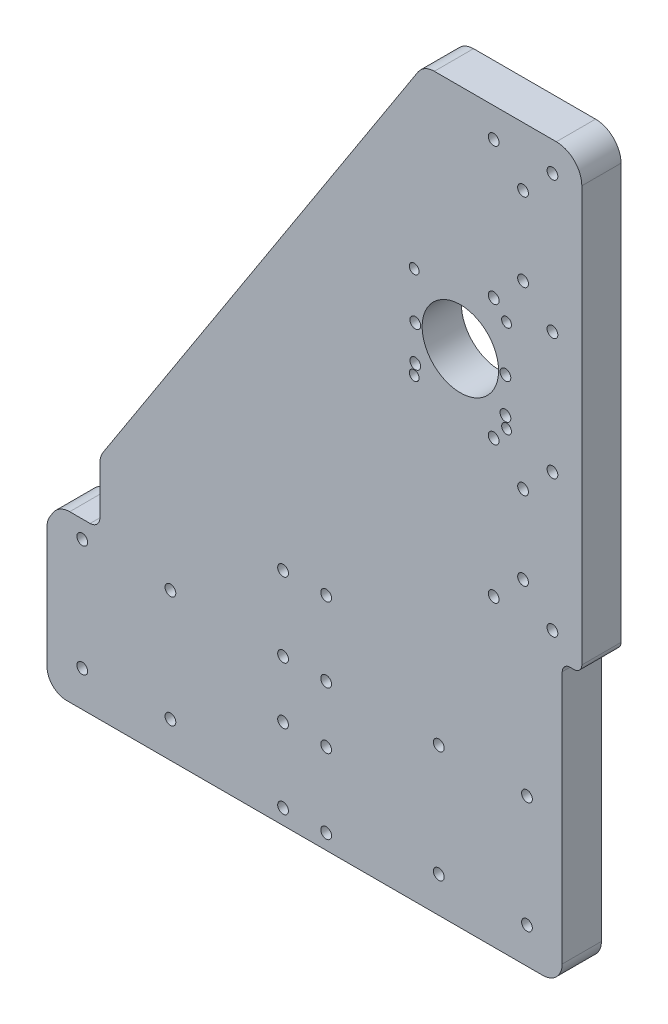
SolidWorks part; units mm, degrees
ref_plane "Front Plane" through (0, 0, 0) normal (0, 0, 1) x (1, 0, 0)
ref_plane "Top Plane" through (0, 0, 0) normal (0, 1, 0) x (1, 0, 0)
ref_plane "Right Plane" through (0, 0, 0) normal (1, 0, 0) x (0, 0, -1)
sketch "Sketch2" plane through (0, 0, 94) normal (0, 0, 1) x (1, 0, 0)
  line L1 (2186.978, 819.9095) -> (2457.8071, 819.9095)
  line L2 (2186.978, 819.9095) -> (2186.978, 457.9095)
  line L3 (2186.978, 457.9095) -> (2457.8071, 457.9095)
  line L4 (2457.8071, 819.9095) -> (2457.8071, 457.9095)
  line L6 (2441.9071, 819.9095) -> (2454.8071, 819.9095) construction
extrude "Boss-Extrude1" add sketch "Sketch2" along normal blind 20
sketch "Sketch3" plane through (0, 0, 114) normal (0, 0, 1) x (1, 0, 0)
  line L0 (2186.978, 819.9095) -> (2186.978, 457.9095) construction
  line L1 (2186.978, 840.163) -> (2194.8071, 840.163)
  line L2 (2186.978, 840.163) -> (2186.978, 445.0092)
  line L3 (2186.978, 445.0092) -> (2194.8071, 445.0092)
  line L4 (2194.8071, 840.163) -> (2194.8071, 445.0092)
extrude "Cut-Extrude1" cut sketch "Sketch3" against normal blind 20
sketch "Sketch4" plane through (0, 0, 114) normal (0, 0, 1) x (1, 0, 0)
  line L0 (2194.8071, 532.657) -> (2380.6092, 819.9095)
  line L1 (2194.8071, 457.9095) -> (2194.8071, 819.9095) construction
  line L2 (2457.8071, 819.9095) -> (2194.8071, 819.9095) construction
  line L3 (2380.6092, 819.9095) -> (2194.8071, 819.9095)
  line L4 (2194.8071, 819.9095) -> (2194.8071, 532.657)
extrude "Cut-Extrude2" cut sketch "Sketch4" against normal blind 20
fillet "Fillet1" radius 10 4 edges at (2457.8071, 457.9095, 104) (2194.8071, 457.9095, 104) (2194.8071, 532.657, 104) (2380.6092, 819.9095, 104)
hole_wizard "M5 Clearance Hole1" positions "Sketch5" profile "Sketch6" hole size "M5" standard "ISO" end condition through all
sketch "Sketch5" plane through (0, 0, 114) normal (0, 0, 1) x (1, 0, 0)
  line L5 (2212.8071, 533.1607) -> (2257.8071, 533.1607) construction
  line L6 (2257.8071, 533.1607) -> (2257.8071, 476.1607) construction
  line L7 (2257.8071, 476.1607) -> (2212.8071, 476.1607) construction
  line L8 (2212.8071, 476.1607) -> (2212.8071, 533.1607) construction
  line L9 (2308.0075, 570.6607) -> (2367.4082, 570.6607) construction
  line L12 (2315.3071, 608.2293) -> (2315.3071, 465.6607) construction
  point P0 (2212.8071, 533.1607)
  point P2 (2257.8071, 533.1607)
  point P4 (2257.8071, 476.1607)
  point P6 (2212.8071, 476.1607)
  point P23 (2439.8071, 476.1607)
  point P24 (2394.8071, 476.1607)
  point P25 (2394.8071, 533.1607)
  point P26 (2439.8071, 533.1607)
  point P27 (2315.3071, 503.6607)
  point P29 (2337.3071, 503.6607)
  point P31 (2315.3071, 465.6607)
  point P33 (2337.3071, 465.6607)
  point P85 (2337.3071, 532.6607)
  point P87 (2315.3071, 532.6607)
  point P89 (2315.3071, 570.6607)
  point P91 (2337.3071, 570.6607)
  point P94 (2337.3071, 532.6607)
  point P95 (2394.8071, 533.1607)
  point P96 (2337.3071, 532.6607)
  dimension "D1" = 45
  dimension "D2" = 57
  dimension "D3" = 45
  dimension "D7" = 22
  dimension "D8" = 38
  dimension "D9" = 22
  dimension "D10" = 38
  dimension "D11" = 57.5
sketch "Sketch6" plane through (2212.8071, 533.1607, 114) normal (1, 0, 0) x (0, -1, 0)
  line L0 (0, 0) -> (0, 20)
  line L1 (0, 20) -> (2.75, 20)
  line L2 (2.75, 20) -> (2.75, 0)
  line L5 (2.75, 0) -> (0, 0)
  line L11 (0, -6.35) -> (0, 107.95) construction
  dimension "Thru Hole Dia." = 5.5
  dimension "Thru Hole Depth" = 20
fillet "Fillet2" radius 3 1 edges at (2457.8071, 819.9095, 104)
hole_wizard "M5 Clearance Hole2" positions "Sketch7" profile "Sketch8" hole size "M5" standard "ISO" end condition through all
sketch "Sketch7" plane through (0, 0, 114) normal (0, 0, 1) x (1, 0, 0)
  point P0 (2422.8071, 612.9095)
  point P2 (2437.8071, 627.9095)
  point P4 (2452.8071, 612.9095)
  point P6 (2452.8071, 682.9095)
  point P8 (2437.8071, 667.9095)
  point P10 (2422.8071, 682.9095)
  point P12 (2452.8071, 744.9095)
  point P14 (2422.8071, 814.9095)
  point P16 (2452.8071, 814.9095)
  point P18 (2422.8071, 744.9095)
  point P20 (2437.8071, 759.9095)
  point P22 (2437.8071, 799.9095)
sketch "Sketch8" plane through (2422.8071, 612.9095, 114) normal (1, 0, 0) x (0, -1, 0)
  line L0 (0, 0) -> (0, 20)
  line L1 (0, 20) -> (2.75, 20)
  line L2 (2.75, 20) -> (2.75, 0)
  line L5 (2.75, 0) -> (0, 0)
  line L11 (0, -6.35) -> (0, 107.95) construction
  dimension "Thru Hole Dia." = 5.5
  dimension "Thru Hole Depth" = 20
hole_wizard "M5 Clearance Hole3" positions "Sketch9" profile "Sketch10" hole size "M5" standard "ISO" end condition through all
sketch "Sketch9" plane through (0, 0, 94) normal (0, 0, -1) x (-1, 0, 0)
  point P0 (-2428.8071, 713.9095)
  point P2 (-2428.8071, 695.9095)
  point P4 (-2382.8071, 695.9095)
  point P6 (-2382.8071, 713.9095)
sketch "Sketch10" plane through (2428.8071, 713.9095, 94) normal (1, 0, 0) x (0, 1, 0)
  line L0 (0, 0) -> (0, 20)
  line L1 (0, 20) -> (2.75, 20)
  line L2 (2.75, 20) -> (2.75, 0)
  line L5 (2.75, 0) -> (0, 0)
  line L11 (0, -6.35) -> (0, 107.95) construction
  dimension "Thru Hole Dia." = 5.5
  dimension "Thru Hole Depth" = 20
sketch "Sketch11" plane through (0, 0, 114) normal (0, 0, 1) x (1, 0, 0)
  circle A3 centre (2405.8071, 713.9095) radius 19.5
  dimension "D1" = 19.5
extrude "Cut-Extrude4" cut sketch "Sketch11" against normal blind 32.2668
sketch "Sketch12" plane through (0, 0, 114) normal (0, 0, 1) x (1, 0, 0)
  line L10 (2221.8071, 542.1607) -> (2195.8071, 542.1607)
  line L11 (2221.8071, 575.6607) -> (2221.8071, 542.1607)
  line L12 (2221.8071, 575.6607) -> (2195.8071, 542.1607)
extrude "Cut-Extrude5" cut sketch "Sketch12" against normal blind 20
fillet "Fillet3" radius 10 2 edges at (2221.8071, 574.3993, 104) (2200.9543, 542.1607, 104)
fillet "Fillet4" radius 5 1 edges at (2221.8071, 542.1607, 104)
hole_wizard "Tap Drill for M6 Tap1" positions "Sketch13" profile "Sketch14" hole size "M6" standard "ISO" end condition through all
sketch "Sketch13" plane through (0, 0, 94) normal (0, 0, -1) x (-1, 0, 0)
  point P0 (-2429.3771, 737.4795)
  point P2 (-2382.2371, 737.4795)
  point P4 (-2429.3771, 690.3395)
  point P6 (-2382.2371, 690.3395)
sketch "Sketch14" plane through (2429.3771, 737.4795, 94) normal (1, 0, 0) x (0, 1, 0)
  line L0 (0, 0) -> (0, 20)
  line L1 (0, 20) -> (2.5, 20)
  line L2 (2.5, 20) -> (2.5, 0)
  line L5 (2.5, 0) -> (0, 0)
  line L11 (0, -6.35) -> (0, 107.95) construction
  dimension "Thru Hole Dia." = 5
  dimension "Thru Hole Depth" = 20
sketch "Sketch15" plane through (0, 0, 114) normal (0, 0, 1) x (1, 0, 0)
  line L0 (2457.8071, 467.9095) -> (2457.8071, 816.9095) construction
  line L1 (2454.8071, 819.9095) -> (2386.0506, 819.9095) construction
  line L2 (2457.8071, 597.1048) -> (2457.8071, 816.9095)
  line L3 (2454.8071, 819.9095) -> (2386.0506, 819.9095)
  line L4 (2467.8071, 605.1048) -> (2467.8071, 816.9095)
  line L5 (2454.8071, 829.9095) -> (2392.5188, 829.9095)
  line L6 (2463.8071, 601.1048) -> (2461.8071, 601.1048)
  line L7 (2223.4105, 576.8782) -> (2377.654, 815.3406) construction
  line L8 (2377.654, 815.3406) -> (2384.1222, 825.3406)
  line L9 (2467.8071, 467.9095) -> (2467.8071, 816.9095) construction
  line L10 (2457.8071, 467.9095) -> (2457.8071, 816.9095) construction
  line L11 (2454.8071, 829.9095) -> (2386.0506, 829.9095) construction
  line L12 (2457.8071, 597.1048) -> (2457.8071, 582.296)
  arc A0 (2386.0506, 819.9095) -> (2377.654, 815.3406) centre (2386.0506, 809.9095) ccw construction
  arc A1 (2457.8071, 816.9095) -> (2454.8071, 819.9095) centre (2454.8071, 816.9095) ccw construction
  arc A2 (2386.0506, 819.9095) -> (2377.654, 815.3406) centre (2386.0506, 809.9095) ccw
  arc A3 (2457.8071, 816.9095) -> (2454.8071, 819.9095) centre (2454.8071, 816.9095) ccw
  arc A4 (2467.8071, 816.9095) -> (2454.8071, 829.9095) centre (2454.8071, 816.9095) ccw
  arc A5 (2463.8071, 601.1048) -> (2467.8071, 605.1048) centre (2463.8071, 605.1048) ccw
  arc A6 (2386.0506, 829.9095) -> (2369.2574, 820.7718) centre (2386.0506, 809.9095) ccw construction
  arc A7 (2457.8071, 597.1048) -> (2461.8071, 601.1048) centre (2461.8071, 597.1048) cw
  arc A8 (2384.1222, 825.3406) -> (2392.5188, 829.9095) centre (2392.5188, 819.9095) cw
  dimension "D2" = 4
  dimension "D3" = 10
  dimension "D1" = 10
extrude "Boss-Extrude2" add sketch "Sketch15" against normal blind 20 contours A8 L8 A7 L6 A5 L4 A4 L5 region at (2460.3036, 707.0072, 114)
